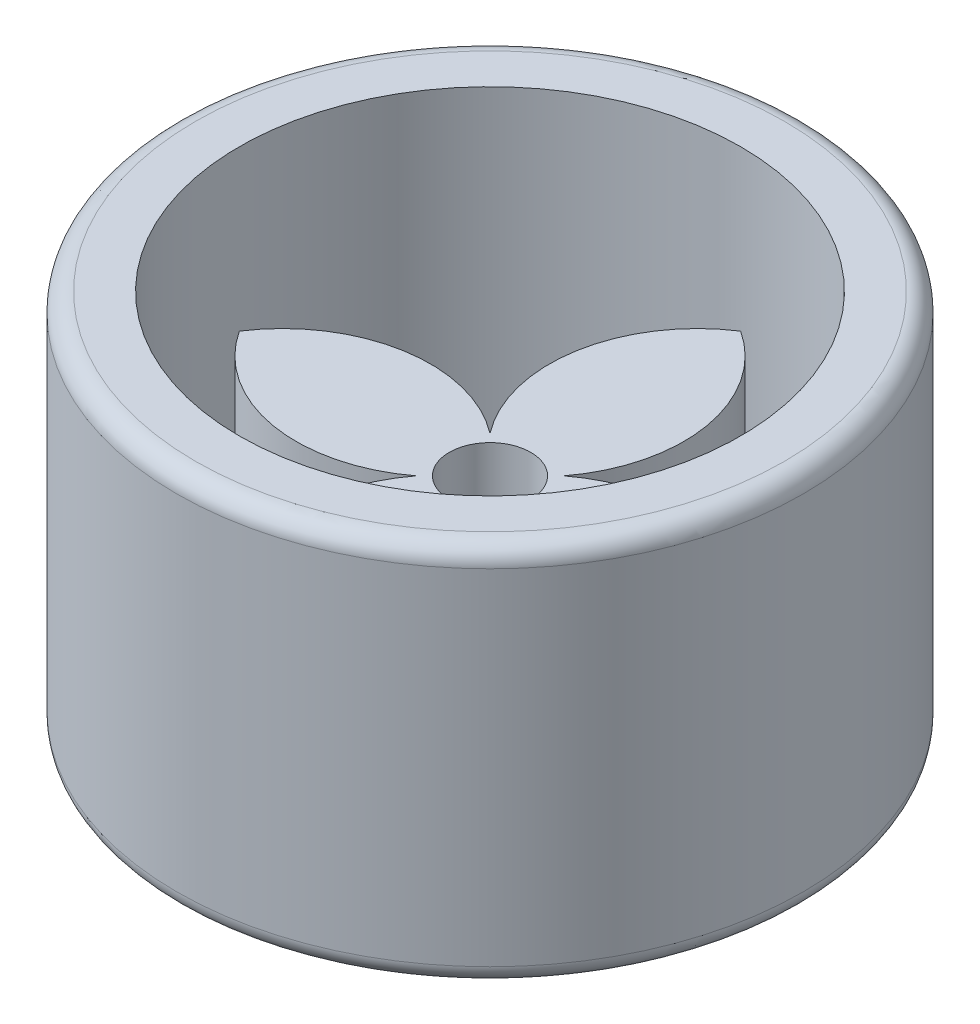
SolidWorks part; units mm, degrees
material "Rubber"
ref_plane "Front Plane" through (0, 0, 0) normal (0, 0, 1) x (1, 0, 0)
ref_plane "Top Plane" through (0, 0, 0) normal (0, 1, 0) x (1, 0, 0)
ref_plane "Right Plane" through (0, 0, 0) normal (1, 0, 0) x (0, 0, -1)
sketch "Sketch1" plane through (0, 0, 0) normal (0, 1, 0) x (1, 0, 0)
  line L0 (-2.635, 0) -> (50, 0) construction
  circle A0 centre (0, 0) radius 50
  circle A1 centre (0, 0) radius 2.635
  circle A2 centre (0, 0) radius 40
  arc A3 (5.877, 5.877) -> (40, 0) centre (20.2122, -12.8908) cw
  arc A4 (5.877, -5.877) -> (40, 0) centre (20.2122, 12.8908) ccw
  arc A5 (5.877, -5.877) -> (0, -40) centre (-12.8908, -20.2122) cw
  arc A6 (-5.877, -5.877) -> (0, -40) centre (12.8908, -20.2122) ccw
  arc A7 (-5.877, -5.877) -> (-40, 0) centre (-20.2122, 12.8908) cw
  arc A8 (-5.877, 5.877) -> (-40, 0) centre (-20.2122, -12.8908) ccw
  arc A9 (-5.877, 5.877) -> (0, 40) centre (12.8908, 20.2122) cw
  arc A10 (5.877, 5.877) -> (0, 40) centre (-12.8908, 20.2122) ccw
  circle A11 centre (0, 0) radius 8.3114 construction
  point P36 (0, 0)
  dimension "D1" = 100
  dimension "D2" = 5.27
  dimension "D3" = 10
  dimension "D4" = 4
  dimension "D5" = 23.6163
  dimension "D6" = 16.6228
extrude "Boss-Extrude1" add sketch "Sketch1" along normal blind 61 contours A2 A0 A8 region at (-48.5858, 0, 0)
extrude "Boss-Extrude2" add sketch "Sketch1<3>" along normal offset from surface (35.5 mm away) 25.5 separate body contours A1 A3 A10 A9 A8 A7 A6 A5 A4 region at (24.0286, 0, 9.2679) up to face at (0, 61, 40)
sketch "Sketch1<3>" plane through (0, 0, 0) normal (0, 1, 0) x (1, 0, 0) same geometry as "Sketch1"
fillet "Fillet1" radius 3 2 edges at (0, 61, 50) (0, 0, 50)
sketch "Sketch2" plane through (0, 35.5, 0) normal (0, 1, 0) x (1, 0, 0)
  circle A0 centre (0, 0) radius 6.5
  dimension "D1" = 13
extrude "Cut-Extrude1" cut sketch "Sketch2" against normal blind 14.6
sketch "Sketch3" plane through (0, 20.9, 0) normal (0, 1, 0) x (1, 0, 0)
  line L0 (-1.5328, 1.975) -> (1.5328, 1.975)
  line L1 (-1.5328, -1.975) -> (1.5328, -1.975)
  line L2 (2.3094, 4) -> (-2.3094, 4)
  line L3 (-2.3094, 4) -> (-4.6188, 0)
  line L4 (-4.6188, 0) -> (-2.3094, -4)
  line L5 (-2.3094, -4) -> (2.3094, -4)
  line L6 (2.3094, -4) -> (4.6188, 0)
  line L7 (4.6188, 0) -> (2.3094, 4)
  line L8 (-2.3877, 0) -> (2.2311, 0) construction
  arc A0 (-1.5328, 1.975) -> (-1.5328, -1.975) centre (0, 0) ccw
  circle A1 centre (0, 0) radius 4 construction
  circle A2 centre (0, 0) radius 4.95
  arc A3 (1.5328, 1.975) -> (-1.5328, 1.975) centre (0, 0) ccw construction
  arc A4 (1.5328, -1.975) -> (1.5328, 1.975) centre (0, 0) ccw
  arc A5 (-1.5328, -1.975) -> (1.5328, -1.975) centre (0, 0) ccw construction
  circle M13 centre (0, 0) radius 2.635
  dimension "D1" = 5
  dimension "D3" = 9.9
  dimension "D4" = 8
  dimension "D2" = 3.95
  dimension "D5" = 9.2376
  dimension "D6" = 4.6188
extrude "Cut-Extrude2" cut sketch "Sketch3" against normal blind 1 contours A2
extrude "Cut-Extrude3" cut sketch "Sketch3<3>" against normal blind 7.95 from surface contours L6 L7 L2 L3 L4 L5 M13 region at (3.3583, 20.9, -1.9389) starting at face at (0, 19.9, 2.635)
sketch "Sketch3<3>" plane through (0, 20.9, 0) normal (0, 1, 0) x (1, 0, 0) same geometry as "Sketch3"
